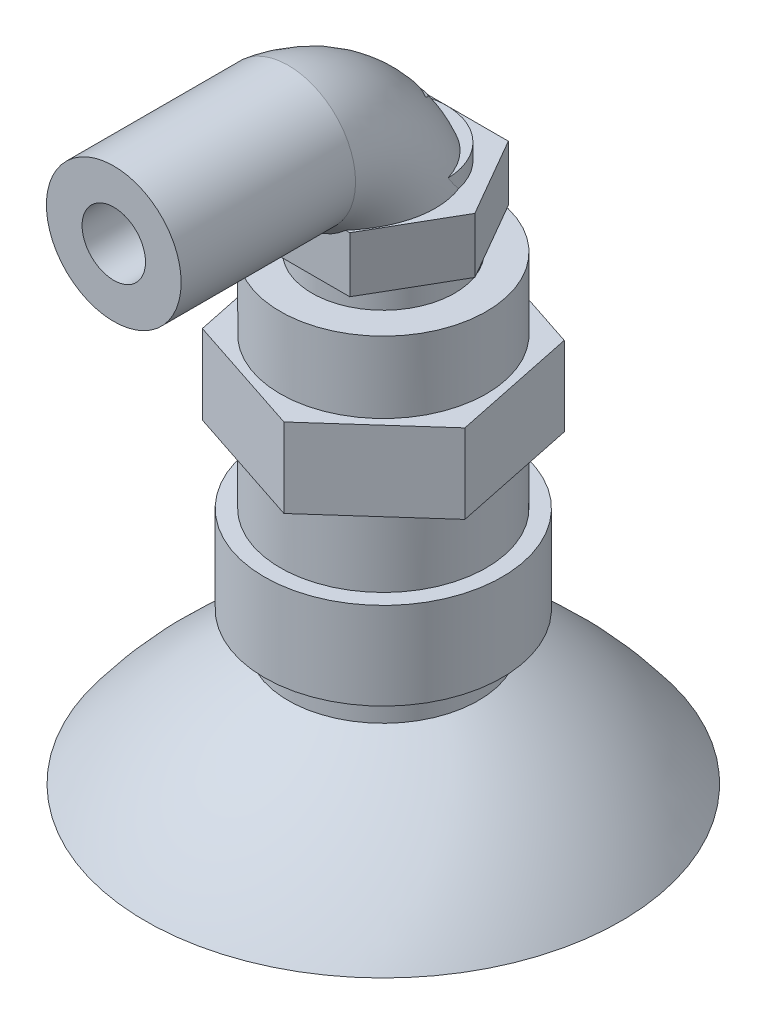
SolidWorks part; units mm, degrees
ref_plane "Front Plane" through (0, 0, 0) normal (0, 0, 1) x (1, 0, 0)
ref_plane "Top Plane" through (0, 0, 0) normal (0, 1, 0) x (1, 0, 0)
ref_plane "Right Plane" through (0, 0, 0) normal (1, 0, 0) x (0, 0, -1)
sketch "Sketch1" plane through (0, 0, 0) normal (0, 0, 1) x (1, 0, 0)
  line L0 (0, 0) -> (0, 47) construction
  line L2 (6, 7.5468) -> (6, 8.5468)
  line L3 (6, 8.5468) -> (5, 8.5468)
  line L4 (5, 8.5468) -> (5, 9.5468)
  line L5 (5, 9.5468) -> (7.5, 9.5468)
  line L6 (7.5, 9.5468) -> (7.5, 15.0468)
  line L7 (7.5, 15.0468) -> (6.5, 15.0468)
  line L8 (6.5, 15.0468) -> (6.5, 29.0468)
  line L9 (6.5, 29.0468) -> (4.5, 29.0468)
  line L10 (4.5, 29.0468) -> (4.5, 30.5468)
  line L11 (4.5, 30.5468) -> (0, 30.5468)
  line L12 (0, 0) -> (0, 30.5468) construction
  line L15 (15, 0) -> (14.3728, 0)
  line L17 (5.7756, 7.1) -> (5.5749, 7.1)
  line L18 (5.5749, 7.1) -> (4, 7.1)
  line L19 (4, 7.1) -> (4, 7)
  line L20 (4, 7) -> (0, 7)
  line L21 (0, 7) -> (0, 30.5468)
  arc A0 (6, 7.5468) -> (15, 0) centre (-5.4442, -15.2409) cw
  arc A2 (5.7756, 7.1) -> (14.3728, 0) centre (-5.4442, -15.2409) cw
  arc A4 (5.7756, 7.1) -> (14.5991, -0.2988) centre (-5.4442, -15.2409) cw construction
  point P24 (6.5, 32.5505)
  point P25 (4.5, 30.5983)
  point P26 (7.5, 16.4823)
  point P27 (7.5, 15.5426)
  point P28 (6.5, 29.5963)
  point P29 (4.5, 31.0963)
  point P30 (0, 31.0963)
  dimension "D17" = 25
  dimension "D1" = 47
  dimension "D2" = 30
  dimension "D3" = 0.5
  dimension "D4" = 6
  dimension "D5" = 1
  dimension "D6" = 5
  dimension "D7" = 15
  dimension "D8" = 14
  dimension "D9" = 5.5
  dimension "D10" = 13
  dimension "D11" = 4.5
  dimension "D12" = 1.5
  dimension "D13" = 1
  dimension "D14" = 0.1
  dimension "D15" = 4
  dimension "D16" = 7
revolve "Revolve1" add sketch "Sketch1" angle 360 about L0
sketch "Sketch2" plane through (0, 30.5468, 0) normal (0, 1, 0) x (1, 0, 0)
  line L1 (2.8868, -5) -> (5.7735, 0)
  line L2 (5.7735, 0) -> (2.8868, 5)
  line L3 (2.8868, 5) -> (-2.8868, 5)
  line L4 (-2.8868, 5) -> (-5.7735, 0)
  line L5 (-5.7735, 0) -> (-2.8868, -5)
  line L6 (-2.8868, -5) -> (2.8868, -5)
  circle A0 centre (0, 0) radius 5 construction
  dimension "D1" = 10
extrude "Boss-Extrude1" add sketch "Sketch2" along normal blind 3.5
sketch "Sketch3" plane through (0, 34.0468, 0) normal (0, 1, 0) x (1, 0, 0)
  circle A0 centre (0, 0) radius 4
  dimension "D1" = 8
extrude "Boss-Extrude2" add sketch "Sketch3" along normal blind 1
sketch "Sketch4" plane through (0, 0, 0) normal (0, 0, 1) x (1, 0, 0)
  line L0 (-15, 0) -> (15, 0) construction
  circle A0 centre (0, 38) radius 4.25
  circle A1 centre (0, 38) radius 2
  dimension "D1" = 8.5
  dimension "D3" = 4
  dimension "D2" = 38
extrude "Boss-Extrude3" add sketch "Sketch4" along normal blind 11 from offset 6 separate body
sketch "Sketch5" plane through (0, 0, 0) normal (1, 0, 0) x (0, 0, -1)
  line L0 (-6, 33.75) -> (-6, 42.25) construction
  line L1 (4, 35.0468) -> (-4, 35.0468) construction
  arc A0 (-6, 38) -> (0, 30.0315) centre (-7.9969, 30.2532) cw
  point P3 (0, 31.9612)
  point P8 (0, 0)
  dimension "D1" = 8
sketch "Sketch6" plane through (0, 35.0468, 0) normal (0, 1, 0) x (1, 0, 0)
  circle A1 centre (0, 0) radius 4
  circle A2 centre (0, 0) radius 4
  dimension "D1" = 0
sketch "Sketch7" plane through (0, 0, 6) normal (0, 0, -1) x (-1, 0, 0)
  circle A0 centre (0, 38) radius 2 construction
  circle A1 centre (0, 38) radius 4.25
  circle A2 centre (0, 38) radius 4.25
  circle A3 centre (0, 38) radius 2
  dimension "D1" = 0
sweep "Sweep1" add profiles "Sketch7" path "Sketch5"
sketch "Sketch8" plane through (0, 7, 0) normal (0, -1, 0) x (1, 0, 0)
  circle A0 centre (0, 0) radius 2
  dimension "D1" = 4
extrude "Cut-Extrude1" cut sketch "Sketch8" against normal blind 31
ref_plane "Plane1" through (0, 22.0468, 0) normal (0, 1, 0) x (1, 0, 0)
sketch "Sketch9" plane through (0, 22.0468, 0) normal (0, 1, 0) x (1, 0, 0)
  line L1 (6.03, 5.3826) -> (-1.6465, 7.9134)
  line L2 (-1.6465, 7.9134) -> (-7.6765, 2.5308)
  line L3 (-7.6765, 2.5308) -> (-6.03, -5.3826)
  line L4 (-6.03, -5.3826) -> (1.6465, -7.9134)
  line L5 (1.6465, -7.9134) -> (7.6765, -2.5308)
  line L6 (7.6765, -2.5308) -> (6.03, 5.3826)
  circle A0 centre (0, 0) radius 7 construction
  dimension "D1" = 14
extrude "Boss-Extrude4" add sketch "Sketch9" along normal blind 2.5 and the other way blind 2.5
